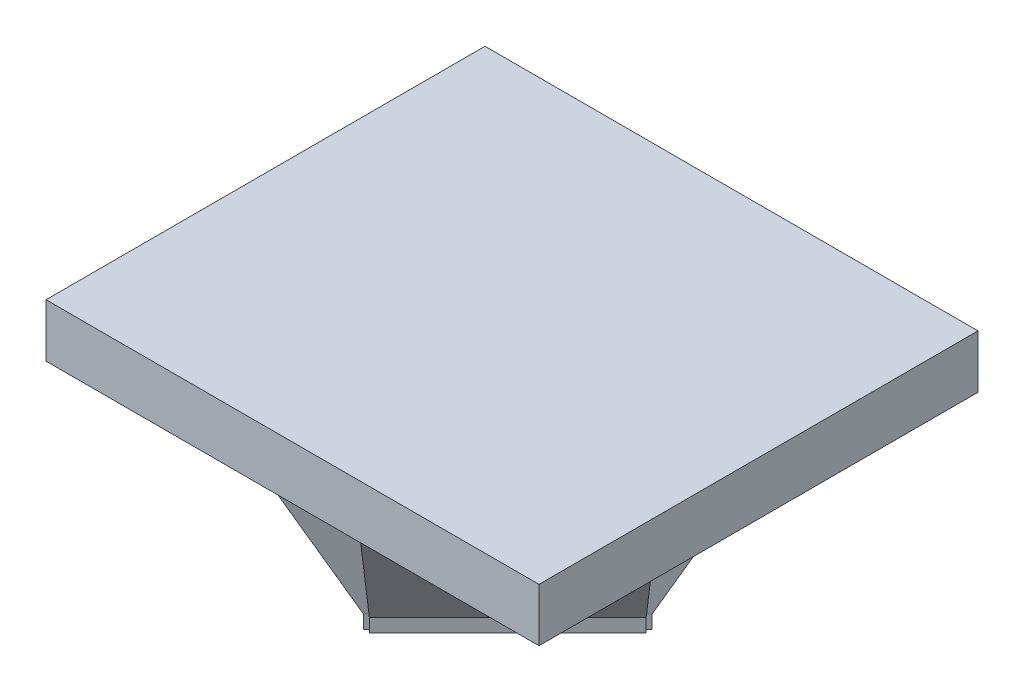
SolidWorks part; units mm, degrees
ref_plane "Front Plane" through (0, 0, 0) normal (0, 0, 1) x (1, 0, 0)
ref_plane "Top Plane" through (0, 0, 0) normal (0, 1, 0) x (1, 0, 0)
ref_plane "Right Plane" through (0, 0, 0) normal (1, 0, 0) x (0, 0, -1)
sketch "Sketch1" plane through (0, 0, 0) normal (0, 1, 0) x (1, 0, 0)
  line L1 (-46.6, 41.5) -> (46.6, 41.5)
  line L2 (-46.6, 41.5) -> (-46.6, -41.5)
  line L3 (-46.6, -41.5) -> (46.6, -41.5)
  line L4 (46.6, 41.5) -> (46.6, -41.5)
  line L5 (-46.6, 41.5) -> (46.6, -41.5) construction
  line L6 (-46.6, -41.5) -> (46.6, 41.5) construction
  point P0 (0, 0)
  dimension "D1" = 83
  dimension "D2" = 93.2
extrude "Boss-Extrude1" add sketch "Sketch1" against normal blind 10.05
sketch "Sketch2" plane through (0, -10.05, 0) normal (0, -1, 0) x (1, 0, 0)
  line L0 (-32.6387, 16.2823) -> (-17.0823, 31.8387) construction
  line L8 (-32.6387, 16.2823) -> (-17.0823, 31.8387) construction
  line L9 (-29.6334, 0.5492) -> (-37.942, 8.8577) construction
  line L10 (-29.6334, 0.5492) -> (-37.942, 8.8577) construction
  line L11 (-9.6577, 37.142) -> (-1.3492, 28.8334) construction
  line L12 (-9.6577, 37.142) -> (-1.3492, 28.8334) construction
  line L13 (15.4823, 31.8387) -> (31.0387, 16.2823) construction
  line L14 (15.4823, 31.8387) -> (31.0387, 16.2823) construction
  line L15 (-0.2508, 28.8334) -> (8.0577, 37.142) construction
  line L16 (-0.2508, 28.8334) -> (8.0577, 37.142) construction
  line L18 (36.342, 8.8577) -> (28.0334, 0.5492) construction
  line L19 (46.6, -41.5) -> (-46.6, 41.5) construction
  line L20 (36.342, 8.8577) -> (28.0334, 0.5492) construction
  line L21 (46.6, 41.5) -> (-46.6, -41.5) construction
  line L40 (31.0387, -16.2823) -> (15.4823, -31.8387) construction
  line L41 (31.0387, -16.2823) -> (15.4823, -31.8387) construction
  line L42 (28.0334, -0.5492) -> (36.342, -8.8577) construction
  line L43 (28.0334, -0.5492) -> (36.342, -8.8577) construction
  line L44 (8.0577, -37.142) -> (-0.2508, -28.8334) construction
  line L45 (8.0577, -37.142) -> (-0.2508, -28.8334) construction
  line L46 (-17.0823, -31.8387) -> (-32.6387, -16.2823) construction
  line L47 (-17.0823, -31.8387) -> (-32.6387, -16.2823) construction
  line L48 (-1.3492, -28.8334) -> (-9.6577, -37.142) construction
  line L49 (-1.3492, -28.8334) -> (-9.6577, -37.142) construction
  line L50 (-37.942, -8.8577) -> (-29.6334, -0.5492) construction
  line L51 (-37.942, -8.8577) -> (-29.6334, -0.5492) construction
  line L76 (-10.7183, -38.2026) -> (-0.8, -28.2843)
  line L77 (-0.8, -28.2843) -> (9.1183, -38.2026)
  line L78 (9.1183, -38.2026) -> (37.4026, -9.9183)
  line L79 (37.4026, -9.9183) -> (27.4843, 0)
  line L80 (27.4843, 0) -> (37.4026, 9.9183)
  line L81 (37.4026, 9.9183) -> (9.1183, 38.2026)
  line L82 (9.1183, 38.2026) -> (-0.8, 28.2843)
  line L83 (-0.8, 28.2843) -> (-10.7183, 38.2026)
  line L84 (-39.0026, 9.9183) -> (-10.7183, 38.2026)
  line L85 (-39.0026, 9.9183) -> (-29.0843, 0)
  line L86 (-29.0843, 0) -> (-39.0026, -9.9183)
  line L87 (-39.0026, -9.9183) -> (-10.7183, -38.2026)
ref_plane "Plane1" through (0, -36.25, 0) normal (0, -1, 0) x (-1, 0, 0)
sketch "Sketch3" plane through (0, -36.25, 0) normal (0, -1, 0) x (-1, 0, 0)
  line L0 (0.2508, 28.8334) -> (-28.0334, 0.5492) construction
  line L2 (1.3492, -28.8334) -> (29.6334, -0.5492) construction
  line L4 (-28.0334, -0.5492) -> (0.2508, -28.8334) construction
  line L5 (1.3492, 28.8334) -> (29.6334, 0.5492) construction
  line L6 (29.6334, -0.5492) -> (29.0843, 0) construction
  line L7 (29.0843, 0) -> (29.6334, 0.5492) construction
  line L8 (1.3492, 28.8334) -> (0.8, 28.2843) construction
  line L9 (0.8, 28.2843) -> (0.2508, 28.8334) construction
  line L10 (-28.0334, 0.5492) -> (-27.4843, 0) construction
  line L11 (-27.4843, 0) -> (-28.0334, -0.5492) construction
  line L12 (1.3492, -28.8334) -> (0.8, -28.2843) construction
  line L13 (0.8, -28.2843) -> (0.2508, -28.8334) construction
  line L14 (0.2508, 26.7121) -> (-25.9121, 0.5492)
  line L15 (-25.9121, 0.5492) -> (-25.363, 0)
  line L16 (-25.363, 0) -> (-25.9121, -0.5492)
  line L17 (-25.9121, -0.5492) -> (0.2508, -26.7121)
  line L18 (0.8, -26.163) -> (0.2508, -26.7121)
  line L19 (1.3492, -26.7121) -> (0.8, -26.163)
  line L20 (1.3492, -26.7121) -> (27.5121, -0.5492)
  line L21 (27.5121, -0.5492) -> (26.963, 0)
  line L22 (26.963, 0) -> (27.5121, 0.5492)
  line L23 (1.3492, 26.7121) -> (27.5121, 0.5492)
  line L24 (1.3492, 26.7121) -> (0.8, 26.163)
  line L25 (0.8, 26.163) -> (0.2508, 26.7121)
  dimension "D1" = 1.5
loft "Loft3" add profiles "Sketch3", "Sketch2" connector at (-0.8, -36.25, -26.163) connector at (-0.8, -10.05, -28.2843)
sketch "Sketch5" plane through (0, -36.25, 0) normal (0, -1, 0) x (1, 0, 0)
  line L12 (-0.8, -26.163) -> (-0.2508, -26.7121)
  line L13 (-0.2508, -26.7121) -> (25.9121, -0.5492)
  line L14 (25.9121, -0.5492) -> (25.363, 0)
  line L15 (25.363, 0) -> (25.9121, 0.5492)
  line L16 (25.9121, 0.5492) -> (-0.2508, 26.7121)
  line L17 (-0.2508, 26.7121) -> (-0.8, 26.163)
  line L18 (-0.8, 26.163) -> (-1.3492, 26.7121)
  line L19 (-1.3492, 26.7121) -> (-27.5121, 0.5492)
  line L20 (-27.5121, 0.5492) -> (-26.963, 0)
  line L21 (-26.963, 0) -> (-27.5121, -0.5492)
  line L22 (-27.5121, -0.5492) -> (-1.3492, -26.7121)
  line L23 (-1.3492, -26.7121) -> (-0.8, -26.163)
  line L24 (-0.8, -26.163) -> (-0.2508, -26.7121)
  line L25 (-0.2508, -26.7121) -> (25.9121, -0.5492)
  line L26 (25.9121, -0.5492) -> (25.363, 0)
  line L27 (25.363, 0) -> (25.9121, 0.5492)
  line L28 (25.9121, 0.5492) -> (-0.2508, 26.7121)
  line L29 (-0.2508, 26.7121) -> (-0.8, 26.163)
  line L30 (-0.8, 26.163) -> (-1.3492, 26.7121)
  line L31 (-1.3492, 26.7121) -> (-27.5121, 0.5492)
  line L32 (-27.5121, 0.5492) -> (-26.963, 0)
  line L33 (-26.963, 0) -> (-27.5121, -0.5492)
  line L34 (-27.5121, -0.5492) -> (-1.3492, -26.7121)
  line L35 (-1.3492, -26.7121) -> (-0.8, -26.163)
  dimension "D1" = 0
extrude "Boss-Extrude3" add sketch "Sketch5" along normal blind 2.5
